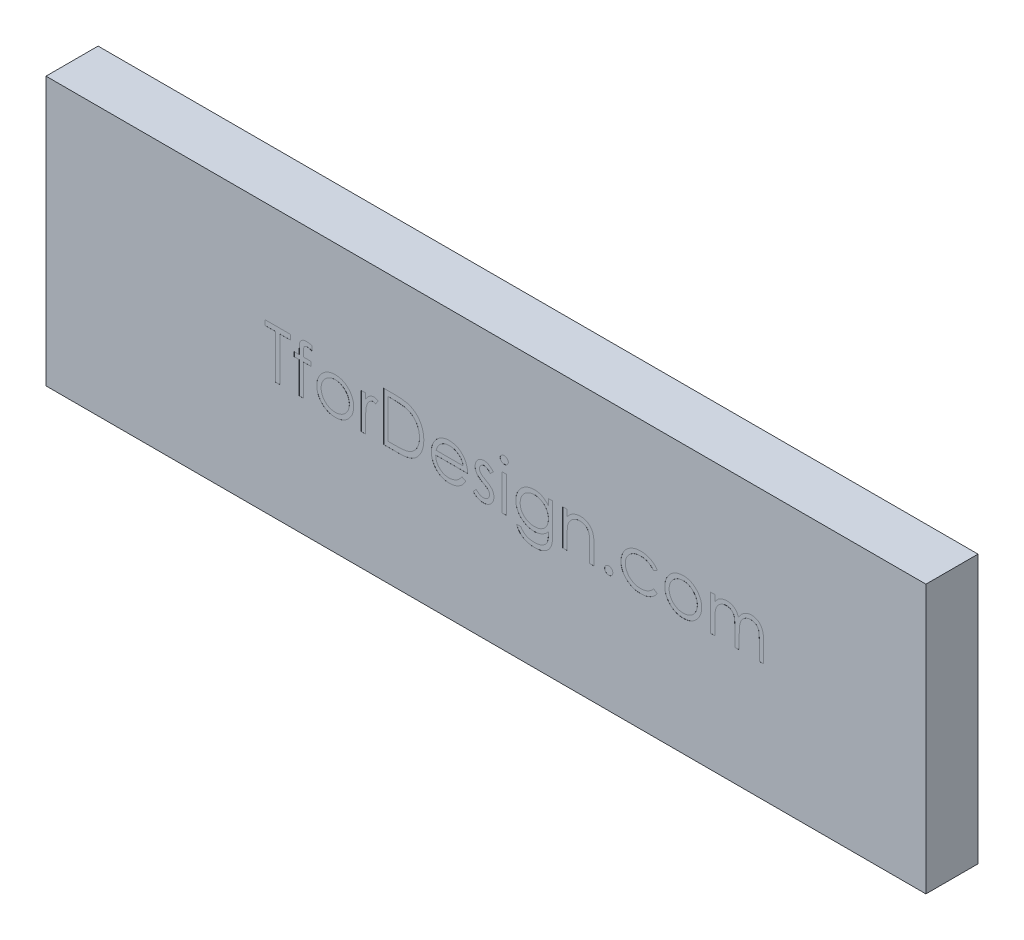
SolidWorks part; units mm, degrees
ref_plane "Front Plane" through (0, 0, 0) normal (0, 0, 1) x (1, 0, 0)
ref_plane "Top Plane" through (0, 0, 0) normal (0, 1, 0) x (1, 0, 0)
ref_plane "Right Plane" through (0, 0, 0) normal (1, 0, 0) x (0, 0, -1)
sketch "Sketch1" plane through (0, 0, 0) normal (0, 0, 1) x (1, 0, 0)
  line L1 (22.3843, -5.4594) -> (-20.5358, -5.4594)
  line L2 (22.3843, -5.4594) -> (22.3843, -18.5448)
  line L3 (22.3843, -18.5448) -> (-20.5358, -18.5448)
  line L4 (-20.5358, -5.4594) -> (-20.5358, -18.5448)
extrude "Boss-Extrude1" add sketch "Sketch1" along normal blind 2.54
sketch "Sketch2" plane through (0, 0, 2.54) normal (0, 0, 1) x (1, 0, 0)
  text T0 "TforDesign.com" font "Century Gothic" height in points 9
extrude "Cut-Extrude1" cut sketch "Sketch2" against normal blind 0.0025
